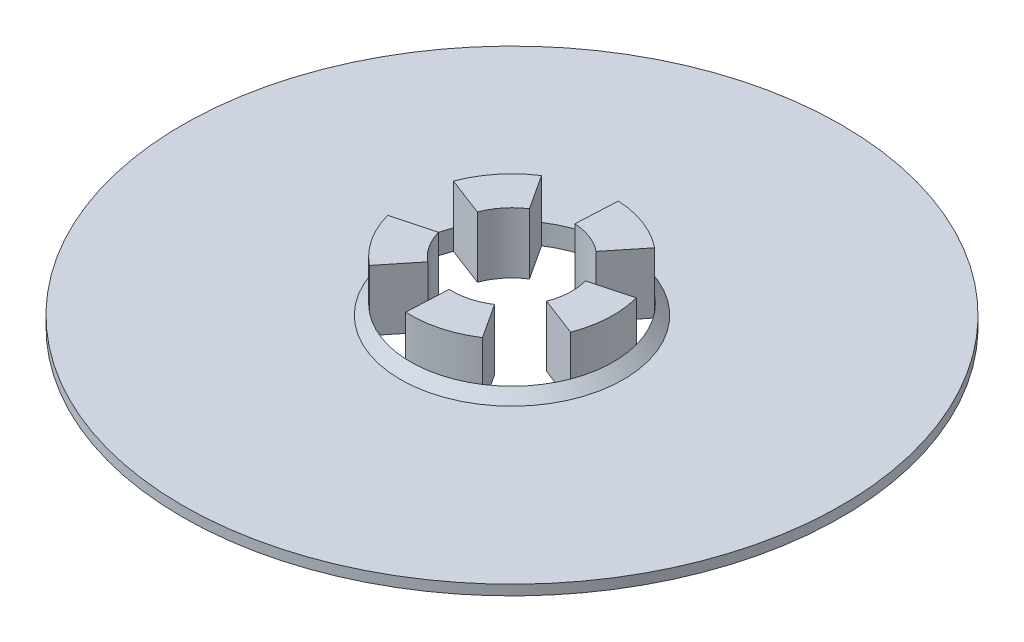
SolidWorks part; units mm, degrees
ref_plane "Front Plane" through (0, 0, 0) normal (0, 0, 1) x (1, 0, 0)
ref_plane "Top Plane" through (0, 0, 0) normal (0, 1, 0) x (1, 0, 0)
ref_plane "Right Plane" through (0, 0, 0) normal (1, 0, 0) x (0, 0, -1)
sketch "Sketch1" plane through (0, 0, 0) normal (0, 1, 0) x (1, 0, 0)
  circle A0 centre (0, 0) radius 41.275
  dimension "D1" = 82.55
extrude "Boss-Extrude1" add sketch "Sketch1" along normal blind 1.27
sketch "Sketch6" plane through (0, 1.27, 0) normal (0, 1, 0) x (1, 0, 0)
  circle A0 centre (0, 0) radius 12.7
  dimension "D1" = 25.4
extrude "Boss-Extrude3" add sketch "Sketch6" along normal blind 6.35
chamfer "Chamfer2" distance 1.27 angle 45 1 edges at (0, 1.27, 12.7)
sketch "Sketch4" plane through (0, 0, 0) normal (0, -1, 0) x (1, 0, 0)
  line L0 (6.9396, 10.6363) -> (4.0982, 6.2813)
  line L1 (11.8662, 4.526) -> (7.0076, 2.6728)
  line L2 (12.2602, -3.3132) -> (7.2403, -1.9566)
  line L3 (7.9713, -9.8868) -> (4.7075, -5.8387)
  line L4 (0.6376, -12.684) -> (0.3765, -7.4905)
  line L5 (-6.9396, -10.6363) -> (-4.0982, -6.2813)
  line L6 (-11.8662, -4.526) -> (-7.0076, -2.6728)
  line L7 (-12.2602, 3.3132) -> (-7.2403, 1.9566)
  line L10 (-7.9713, 9.8868) -> (-4.7075, 5.8387)
  line L11 (-0.6376, 12.684) -> (-0.3765, 7.4905)
  circle A0 centre (0, 0) radius 12.7 construction
  arc A1 (7.0076, 2.6728) -> (4.0982, 6.2813) centre (0, 0) ccw
  arc A2 (11.8662, 4.526) -> (6.9396, 10.6363) centre (0, 0) ccw
  arc A3 (4.7075, -5.8387) -> (7.2403, -1.9566) centre (0, 0) ccw
  arc A4 (7.9713, -9.8868) -> (12.2602, -3.3132) centre (0, 0) ccw
  arc A5 (-4.0982, -6.2813) -> (0.3765, -7.4905) centre (0, 0) ccw
  arc A6 (-6.9396, -10.6363) -> (0.6376, -12.684) centre (0, 0) ccw
  arc A7 (-7.2403, 1.9566) -> (-7.0076, -2.6728) centre (0, 0) ccw
  arc A8 (-12.2602, 3.3132) -> (-11.8662, -4.526) centre (0, 0) ccw
  arc A10 (-0.6376, 12.684) -> (-7.9713, 9.8868) centre (0, 0) ccw
  arc A13 (7.0076, 2.6728) -> (4.0982, 6.2813) centre (0, 0) ccw
  arc A14 (4.7075, -5.8387) -> (7.2403, -1.9566) centre (0, 0) ccw
  arc A16 (-4.0982, -6.2813) -> (0.3765, -7.4905) centre (0, 0) ccw
  arc A17 (-7.2403, 1.9566) -> (-7.0076, -2.6728) centre (0, 0) ccw
  circle A20 centre (0, 0) radius 7.5
  circle A21 centre (0, 0) radius 41.275 construction
  point P40 (0, 0)
  dimension "D1" = 36
  dimension "D2" = 7.5
  dimension "D3" = 12.7
extrude "Cut-Extrude2" cut sketch "Sketch4" against normal through all contours L11 A10 L10 | L1 A2 L0 A1 | L3 A4 L2 A3 | L5 A6 L4 A5 | L7 A8 L6 A7 | A5 A20 A3 A1 A7 region at (7.9049, 0, 6.3733) region at (0, 0, 0) region at (-3.6187, 0, 9.4874) region at (8.5042, 0, -5.5485) region at (-10.1413, 0, -0.5098) region at (-2.649, 0, -9.8025)
